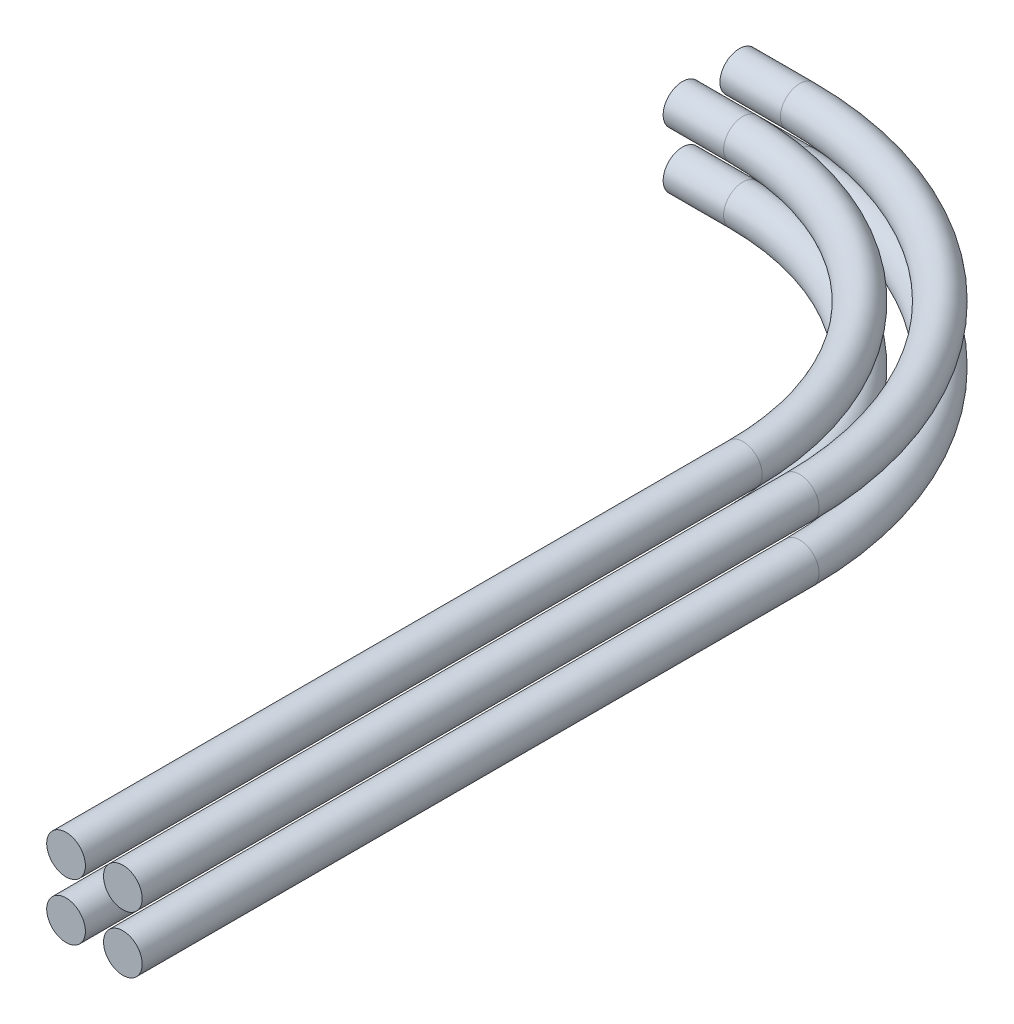
SolidWorks part; units mm, degrees
ref_plane "Front Plane" through (0, 0, 0) normal (0, 0, 1) x (1, 0, 0)
ref_plane "Top Plane" through (0, 0, 0) normal (0, 1, 0) x (1, 0, 0)
ref_plane "Right Plane" through (0, 0, 0) normal (1, 0, 0) x (0, 0, -1)
sketch "Sketch1" plane through (0, 0, 0) normal (0, 1, 0) x (1, 0, 0)
  line L0 (0, 0) -> (5, 0)
  line L1 (33, -28) -> (33, -84)
  line L2 (0, -4.7) -> (5, -4.7)
  line L3 (28.3, -28) -> (28.3, -84)
  line L4 (0, -4.7) -> (0, 0) construction
  line L5 (33, -84) -> (28.3, -84) construction
  line L6 (5, 0) -> (5, -4.7) construction
  line L7 (28.3, -28) -> (33, -28) construction
  arc A0 (5, -4.7) -> (28.3, -28) centre (5, -28) cw
  arc A1 (5, 0) -> (33, -28) centre (5, -28) cw
  point P11 (33, 0)
  dimension "D4" = 28
  dimension "D1" = 4.7
  dimension "D2" = 5
  dimension "D3" = 84
ref_plane "Plane1" through (0, 0, 0) normal (1, 0, 0) x (0, 0, -1)
sketch "Sketch2" plane through (0, 0, 0) normal (1, 0, 0) x (0, 0, -1)
  circle A0 centre (0, 0) radius 1.6
  circle A1 centre (-4.7, 0) radius 1.6
  dimension "D1" = 3.2
sweep "Sweep1" add profiles "Sketch2" path "Sketch1"
sketch "Sketch3" plane through (0, 0, 0) normal (1, 0, 0) x (0, 0, -1)
  line L0 (0, 0) -> (0, 4.7) construction
  dimension "D1" = 4.7
pattern_linear "LPattern1" count 2 spacing 4.7 along (0, 1, 0) of "Sweep1"
